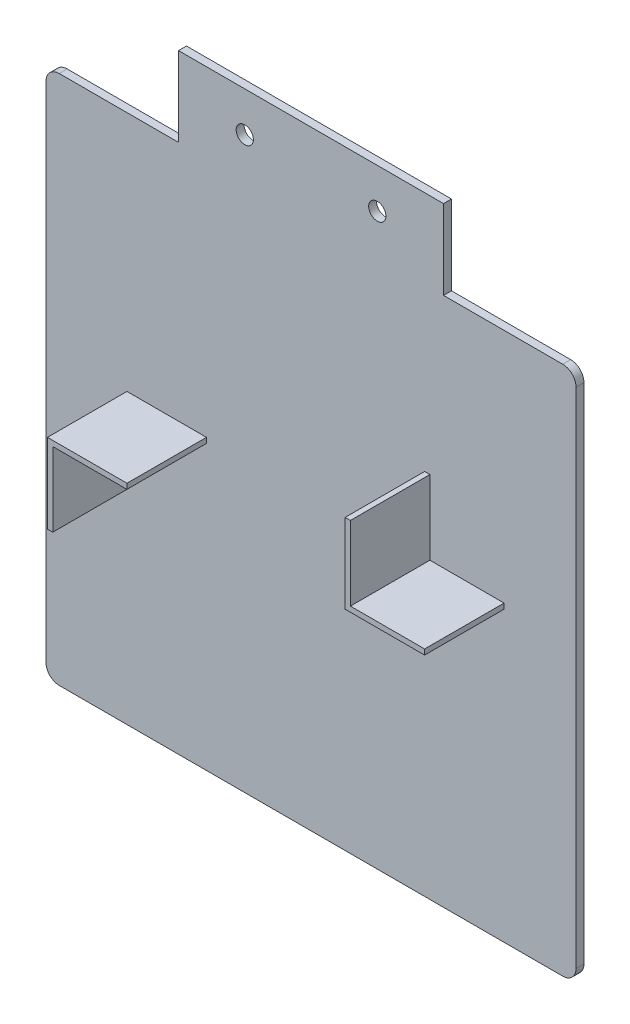
SolidWorks part; units mm, degrees
material "Galvanized Steel"
ref_plane "Front Plane" through (0, 0, 0) normal (0, 0, 1) x (1, 0, 0)
ref_plane "Top Plane" through (0, 0, 0) normal (0, 1, 0) x (1, 0, 0)
ref_plane "Right Plane" through (0, 0, 0) normal (1, 0, 0) x (0, 0, -1)
sketch "Sketch1" plane through (0, 0, 0) normal (0, 0, 1) x (1, 0, 0)
  line L0 (-79.9145, 72.265) -> (-79.9145, 42.265)
  line L1 (20.0855, 72.265) -> (-79.9145, 72.265)
  line L2 (70.0855, 37.265) -> (70.0855, -152.735)
  line L3 (65.0855, -157.735) -> (-124.9145, -157.735)
  line L4 (-129.9145, 37.265) -> (-129.9145, -152.735)
  line L5 (-79.9145, 42.265) -> (-124.9145, 42.265)
  line L6 (20.0855, 72.265) -> (20.0855, 42.265)
  line L7 (20.0855, 42.265) -> (65.0855, 42.265)
  circle A0 centre (-4.9145, 57.265) radius 3.25
  circle A1 centre (-54.9145, 57.265) radius 3.25
  arc A2 (-124.9145, -157.735) -> (-129.9145, -152.735) centre (-124.9145, -152.735) cw
  arc A3 (65.0855, -157.735) -> (70.0855, -152.735) centre (65.0855, -152.735) ccw
  arc A4 (-129.9145, 37.265) -> (-124.9145, 42.265) centre (-124.9145, 37.265) cw
  arc A5 (70.0855, 37.265) -> (65.0855, 42.265) centre (65.0855, 37.265) ccw
  dimension "D4" = 6.5
  dimension "D7" = 6.5
  dimension "D8" = 5
  dimension "D1" = 25
  dimension "D2" = 25
  dimension "D3" = 15
  dimension "D5" = 30
  dimension "D6" = 30
base flange "Base-Flange1" sketch "Sketch1" thickness 3 reverse thickness direction no parameters "D1"=0.7366
sketch "Sketch2" plane through (0, 0, 0) normal (0, 0, 1) x (1, 0, 0)
  line L0 (42.9456, -48.8579) -> (12.9456, -48.8579)
  line L1 (12.9456, -48.8579) -> (12.9456, -18.8579)
  line L2 (-69.3775, -48.8579) -> (-99.3775, -48.8579)
  line L3 (-99.3775, -48.8579) -> (-99.3775, -78.8579)
  line L4 (42.9456, -46.8579) -> (14.9456, -46.8579)
  line L5 (14.9456, -46.8579) -> (14.9456, -18.8579)
  line L6 (-69.3775, -50.8579) -> (-97.3775, -50.8579)
  line L7 (-97.3775, -50.8579) -> (-97.3775, -78.8579)
  line L8 (-69.3775, -50.8579) -> (-69.3775, -48.8579)
  line L9 (-97.3775, -78.8579) -> (-99.3775, -78.8579)
  line L10 (42.9456, -46.8579) -> (42.9456, -48.8579)
  line L11 (14.9456, -18.8579) -> (12.9456, -18.8579)
  dimension "D1" = 30
  dimension "D2" = 30
  dimension "D3" = 30
  dimension "D4" = 30
  dimension "D5" = 2
  dimension "D6" = 2
extrude "Boss-Extrude1" add sketch "Sketch2" along normal blind 30
sketch "Bend-Lines1" [suppressed] plane through (0, 0, 0) normal (0, 1, 0) x (1, 0, 0)
sketch "Bounding-Box1" [suppressed] plane through (0, 0, 0) normal (0, 1, 0) x (1, 0, 0)
sheet metal parameters "Sheet-Metal1" thickness 3 parameters "D1"=0.7366
flat pattern "Flat-Pattern1" [suppressed]
sketch "Bend-Lines2" plane through (0, 0, 0) normal (0, 1, 0) x (1, 0, 0)
sketch3d "Bounding-Box2" [suppressed]
  line L0 (-195, -195, 0) -> (-195, 35, 0) construction
  line L1 (5, -195, 0) -> (5, 35, 0) construction
  line L2 (-195, -195, 0) -> (5, -195, 0) construction
  line L3 (-195, 35, 0) -> (5, 35, 0) construction
sheet metal parameters "Sheet-Metal2" thickness 3 parameters "D1"=0.7366
flat pattern "Flat-Pattern1"
sketch "Bend-Lines2" plane through (0, 0, 0) normal (0, 1, 0) x (1, 0, 0)
sketch3d "Bounding-Box2" [suppressed]
  line L0 (195, -195, 0) -> (195, 35, 0) construction
  line L1 (-5, -195, 0) -> (-5, 35, 0) construction
  line L2 (195, -195, 0) -> (-5, -195, 0) construction
  line L3 (195, 35, 0) -> (-5, 35, 0) construction
